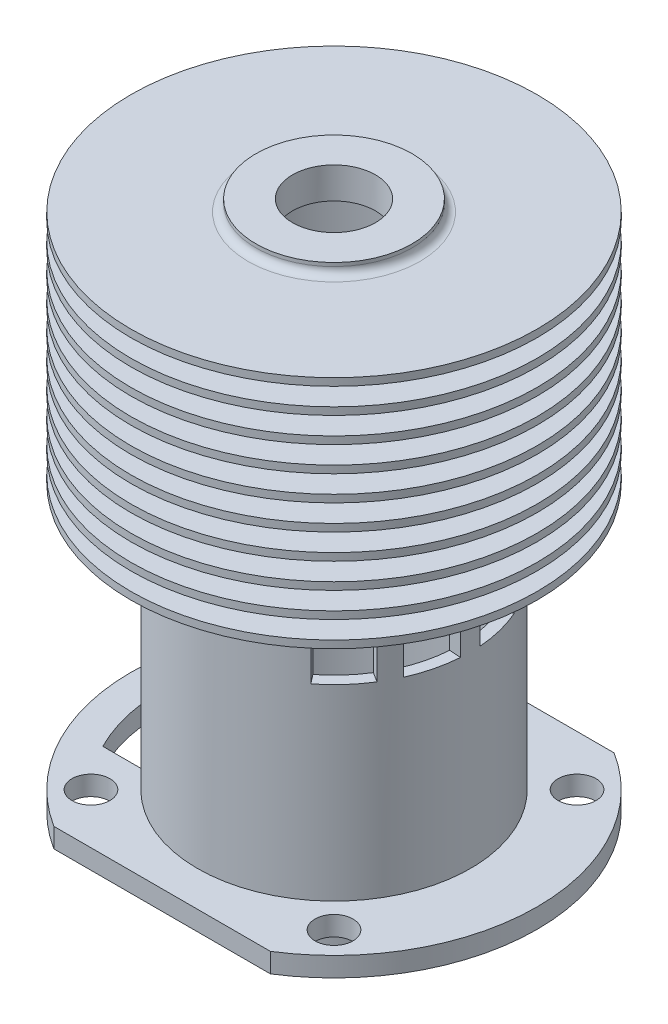
SolidWorks part; units mm, degrees
ref_plane "Front Plane" through (0, 0, 0) normal (0, 0, 1) x (1, 0, 0)
ref_plane "Top Plane" through (0, 0, 0) normal (0, 1, 0) x (1, 0, 0)
ref_plane "Right Plane" through (0, 0, 0) normal (1, 0, 0) x (0, 0, -1)
sketch "Sketch1" plane through (0, 0, 0) normal (0, 0, 1) x (1, 0, 0)
  line L0 (0, 0) -> (0, 63.1419) construction
  line L1 (13.8811, 0) -> (13.8811, 2.7781)
  line L2 (13.8811, 31.75) -> (20.6375, 31.75)
  line L3 (20.6375, 31.75) -> (20.6375, 32.512)
  line L4 (20.6375, 32.512) -> (13.8811, 32.512)
  line L5 (13.8811, 0) -> (12.7, 0)
  line L6 (12.7, 0) -> (12.7, 53.5781)
  line L7 (13.8811, 4.7625) -> (20.6375, 4.7625)
  line L8 (20.6375, 4.7625) -> (20.6375, 2.7781)
  line L9 (20.6375, 2.7781) -> (13.8811, 2.7781)
  line L10 (13.8811, 4.7625) -> (13.8811, 31.75)
  line L11 (13.8811, 34.3154) -> (20.6375, 34.3154)
  line L12 (20.6375, 34.3154) -> (20.6375, 35.0774)
  line L13 (20.6375, 35.0774) -> (13.8811, 35.0774)
  line L14 (13.8811, 36.8808) -> (20.6375, 36.8808)
  line L15 (20.6375, 36.8808) -> (20.6375, 37.6428)
  line L16 (20.6375, 37.6428) -> (13.8811, 37.6428)
  line L17 (13.8811, 39.4462) -> (20.6375, 39.4462)
  line L18 (20.6375, 39.4462) -> (20.6375, 40.2082)
  line L19 (20.6375, 40.2082) -> (13.8811, 40.2082)
  line L20 (13.8811, 42.0116) -> (20.6375, 42.0116)
  line L21 (20.6375, 42.0116) -> (20.6375, 42.7736)
  line L22 (20.6375, 42.7736) -> (13.8811, 42.7736)
  line L23 (13.8811, 44.577) -> (20.6375, 44.577)
  line L24 (20.6375, 44.577) -> (20.6375, 45.339)
  line L25 (20.6375, 45.339) -> (13.8811, 45.339)
  line L26 (13.8811, 47.1424) -> (20.6375, 47.1424)
  line L27 (20.6375, 47.1424) -> (20.6375, 47.9044)
  line L28 (20.6375, 47.9044) -> (13.8811, 47.9044)
  line L29 (13.8811, 49.7078) -> (20.6375, 49.7078)
  line L30 (20.6375, 49.7078) -> (20.6375, 50.4698)
  line L31 (20.6375, 50.4698) -> (13.8811, 50.4698)
  line L32 (13.8811, 52.2732) -> (20.6375, 52.2732)
  line L33 (20.6375, 52.2732) -> (20.6375, 53.0352)
  line L34 (20.6375, 53.0352) -> (13.8811, 53.0352)
  line L35 (13.8811, 54.8386) -> (20.6375, 54.8386)
  line L36 (20.6375, 54.8386) -> (20.6375, 55.6006)
  line L37 (20.6375, 55.6006) -> (13.8811, 55.6006)
  line L38 (13.8811, 31.75) -> (13.8811, 34.3154) construction
  line L39 (13.8811, 32.512) -> (13.8811, 34.3154)
  line L40 (13.8811, 35.0774) -> (13.8811, 36.8808)
  line L41 (13.8811, 37.6428) -> (13.8811, 39.4462)
  line L42 (13.8811, 40.2082) -> (13.8811, 42.0116)
  line L43 (13.8811, 42.7736) -> (13.8811, 44.577)
  line L44 (13.8811, 45.339) -> (13.8811, 47.1424)
  line L45 (13.8811, 47.9044) -> (13.8811, 49.7078)
  line L46 (13.8811, 50.4698) -> (13.8811, 52.2732)
  line L47 (13.8811, 53.0352) -> (13.8811, 54.8386)
  line L48 (0, 56.7531) -> (7.9375, 56.7531)
  line L50 (0, 56.7531) -> (0, 53.5781)
  line L51 (0, 53.5781) -> (12.7, 53.5781)
  line L52 (7.9375, 56.7531) -> (7.9375, 56.3943)
  line L53 (8.7313, 55.6006) -> (13.8811, 55.6006)
  arc A0 (7.9375, 56.3943) -> (8.7313, 55.6006) centre (8.7312, 56.3943) ccw
  point P15 (0, 0)
  dimension "D14" = 0.7937
  dimension "D1" = 25.4
  dimension "D2" = 27.7622
  dimension "D3" = 41.275
  dimension "D4" = 1.9844
  dimension "D5" = 2.7781
  dimension "D6" = 26.9875
  dimension "D7" = 0.762
  dimension "D8" = 41.275
  dimension "D10" = 1.8034
  dimension "D11" = 50.8
  dimension "D12" = 15.875
  dimension "D13" = 3.175
  dimension "D9" = 10
revolve "Revolve1" add sketch "Sketch1" angle 360 about L0
sketch "Sketch2" plane through (0, 56.7531, 0) normal (0, 1, 0) x (1, 0, 0)
  point P0 (0, 0)
hole_wizard "3/8-24 Tapped Hole1" positions "Sketch2" profile "Sketch3" tap size "3/8-24" standard "ANSI Inch" end condition through all
sketch "Sketch3" plane through (0, 56.7531, 0) normal (1, 0, 0) x (0, 0, 1)
  line L0 (0, 0) -> (0, 56.7531)
  line L1 (0, 56.7531) -> (4.2164, 56.7531)
  line L2 (4.2164, 56.7531) -> (4.2164, 0)
  line L5 (4.2164, 0) -> (0, 0)
  line L11 (0, -6.35) -> (0, 107.95) construction
  dimension "Thru Tap Drill Dia." = 8.4328
  dimension "Thru Tap Drill Depth" = 56.7531
cosmetic thread "Hole Thread1" parameters "D2"=9.525
ref_plane "Plane1" through (0, 30.1593, 0) normal (0, -1, 0) x (-1, 0, 0)
sketch "Sketch4" plane through (0, 30.1593, 0) normal (0, -1, 0) x (-1, 0, 0)
  line L0 (0, -12.7) -> (0, -13.8811) construction
  line L1 (-8.5694, -10.9202) -> (-7.8402, -9.991)
  line L2 (-10.7558, -6.7529) -> (-11.7561, -7.381)
  line L3 (-10.3157, -9.2883) -> (-9.4379, -8.498) construction
  line L4 (-10.7558, -6.7529) -> (-9.4379, -8.498) construction
  line L5 (-9.4379, -8.498) -> (-7.8402, -9.991) construction
  line L6 (-12.693, -5.6189) -> (-11.613, -5.1408)
  line L7 (-13.4688, -3.3581) -> (-12.3228, -3.0724) construction
  line L8 (-12.6671, -0.9129) -> (-13.8452, -0.9978)
  line L9 (-13.8452, 0.9978) -> (-12.6671, 0.9129)
  line L10 (-13.4688, 3.3581) -> (-12.3228, 3.0724) construction
  line L11 (-11.613, 5.1408) -> (-12.693, 5.6189)
  line L12 (-11.7561, 7.381) -> (-10.7558, 6.7529)
  line L13 (-10.3157, 9.2883) -> (-9.4379, 8.498) construction
  line L14 (-7.8402, 9.991) -> (-8.5694, 10.9202)
  line L15 (11.4782, -7.8061) -> (10.5016, -7.1419)
  line L16 (13.218, -4.239) -> (12.0933, -3.8783)
  line L17 (12.4763, -6.0851) -> (11.4147, -5.5673) construction
  line L18 (12.0933, -3.8783) -> (11.4147, -5.5673) construction
  line L19 (11.4147, -5.5673) -> (10.5016, -7.1419) construction
  line L20 (13.7385, -1.9844) -> (12.5696, -1.8155)
  line L21 (13.8811, 0) -> (12.7, 0) construction
  line L22 (13.7385, 1.9844) -> (12.5696, 1.8155)
  line L23 (13.218, 4.239) -> (12.0933, 3.8783)
  line L24 (12.4763, 6.0851) -> (11.4147, 5.5673) construction
  line L25 (11.4782, 7.8061) -> (10.5016, 7.1419)
  arc A0 (-7.8402, 9.991) -> (-10.7558, 6.7529) centre (0, 0) ccw
  arc A1 (-8.5694, 10.9202) -> (-11.7561, 7.381) centre (0, 0) ccw
  circle A2 centre (0, 0) radius 12.7 construction
  circle A3 centre (0, 0) radius 13.8811 construction
  circle A4 centre (0, 0) radius 13.8811 construction
  arc A5 (10.5016, -7.1419) -> (12.0933, -3.8783) centre (0, 0) ccw
  arc A6 (11.4782, -7.8061) -> (13.218, -4.239) centre (0, 0) ccw
  arc A7 (12.5696, -1.8155) -> (12.5696, 1.8155) centre (0, 0) ccw
  arc A8 (13.7385, -1.9844) -> (13.7385, 1.9844) centre (0, 0) ccw
  arc A9 (12.0933, 3.8783) -> (10.5016, 7.1419) centre (0, 0) ccw
  arc A10 (13.218, 4.239) -> (11.4782, 7.8061) centre (0, 0) ccw
  arc A11 (-11.613, 5.1408) -> (-12.6671, 0.9129) centre (0, 0) ccw
  arc A12 (-12.693, 5.6189) -> (-13.8452, 0.9978) centre (0, 0) ccw
  arc A13 (-12.6671, -0.9129) -> (-11.613, -5.1408) centre (0, 0) ccw
  arc A14 (-13.8452, -0.9978) -> (-12.693, -5.6189) centre (0, 0) ccw
  arc A15 (-10.7558, -6.7529) -> (-7.8402, -9.991) centre (0, 0) ccw
  arc A16 (-11.7561, -7.381) -> (-8.5694, -10.9202) centre (0, 0) ccw
  dimension "D6" = 3.9688
  dimension "D1" = 4.7625
  dimension "D2" = 48
  dimension "D4" = 12.3228
  dimension "D5" = 12.6671
  dimension "D3" = 11.613
  dimension "D7" = 64
  dimension "D8" = 3
extrude "Cut-Extrude1" cut sketch "Sketch4" along normal blind 6.35 contours L14 A1 L12 A0 | A16 L1 A15 L2 | A14 L6 A13 L8 | A12 L9 A11 L11 region at (9.8344, 30.1593, -8.855)
extrude "Cut-Extrude2" cut sketch "Sketch4<3>" along normal blind 4.7625 contours L23 A10 L25 A9 | L20 A8 L22 A7 | L15 A6 L16 A5 region at (-11.9124, 30.1593, 5.8101) region at (-13.2537, 30.1593, 0) region at (-11.9124, 30.1593, -5.8101)
sketch "Sketch4<3>" plane through (0, 30.1593, 0) normal (0, -1, 0) x (-1, 0, 0) same geometry as "Sketch4"
ref_axis "Axis1" through (0, 30.1593, -24.2662) along (0, 0, 1)
sketch "Sketch5" plane through (0, 2.7781, 0) normal (0, -1, 0) x (1, 0, 0)
  line L0 (0, 0) -> (20.6375, 0) construction
  line L1 (-10.9985, 17.4625) -> (10.9985, 17.4625)
  line L2 (-10.9985, -17.4625) -> (10.9985, -17.4625)
  line L3 (12.3479, 12.3479) -> (0, 0) construction
  line L4 (0, -24.2662) -> (0, 22.1043) construction
  line L5 (0, 0) -> (12.3479, 12.3479) construction
  circle A0 centre (0, 0) radius 20.6375 construction
  arc A1 (10.9985, 17.4625) -> (-10.9985, 17.4625) centre (0, 0) ccw
  arc A2 (-10.9985, -17.4625) -> (10.9985, -17.4625) centre (0, 0) ccw
  circle A3 centre (0, 0) radius 17.4625 construction
  point P11 (12.3479, 12.3479)
  point P18 (12.3479, -12.3479)
  point P19 (-12.3479, -12.3479)
  point P20 (-12.3479, 12.3479)
  point P23 (-12.3479, 12.3479)
  dimension "D2" = 34.925
  dimension "D1" = 17.4625
  dimension "D3" = 45
  dimension "D5" = 17.4625
  dimension "D4" = 4
hole_wizard "#24 (0.152) Diameter Hole1" positions "Sketch5" profile "Sketch7" hole size "#24" standard "ANSI Inch" end condition up to next
sketch "Sketch7" plane through (-12.3479, 2.7781, 12.3479) normal (1, 0, 0) x (0, 0, -1)
  line L0 (0, 0) -> (0, 1.9844)
  line L1 (0, 1.9844) -> (1.9304, 1.9844)
  line L2 (1.9304, 1.9844) -> (1.9304, 0)
  line L5 (1.9304, 0) -> (0, 0)
  line L11 (0, -6.35) -> (0, 107.95) construction
  dimension "Thru Hole Dia." = 3.8608
  dimension "Thru Hole Depth" = 1.9844
extrude "Cut-Extrude3" cut sketch "Sketch5<2>" against normal up to next
sketch "Sketch5<2>" plane through (0, 2.7781, 0) normal (0, -1, 0) x (1, 0, 0) same geometry as "Sketch5"
sketch "Sketch9" plane through (0, 2.7781, 0) normal (0, -1, 0) x (1, 0, 0)
  line L0 (-20.6375, 0) -> (20.6375, 0) construction
  line L5 (0, 20.6375) -> (0, -20.6375) construction
  line L6 (0, -24.2662) -> (0, 22.1043) construction
  line L7 (-13.471, 0) -> (-13.471, -7.9375) construction
  line L8 (-13.471, 7.9375) -> (-13.471, 0) construction
  line L9 (-11.3878, -7.9375) -> (-15.5543, -7.9375)
  line L10 (-11.3878, 7.9375) -> (-15.5543, 7.9375)
  arc A0 (-10.9985, 17.4625) -> (-10.9985, -17.4625) centre (0, 0) ccw construction
  arc A1 (10.9985, -17.4625) -> (10.9985, 17.4625) centre (0, 0) ccw construction
  circle A6 centre (0, 0) radius 20.6375 construction
  arc A7 (-11.3878, 7.9375) -> (-11.3878, -7.9375) centre (0, 0) ccw
  arc A8 (-15.5543, -7.9375) -> (-15.5543, 7.9375) centre (0, 0) cw
  dimension "D2" = 17.4625
  dimension "D1" = 13.8811
  dimension "D3" = 22.3863
extrude "Cut-Extrude4" cut sketch "Sketch9" against normal up to next
